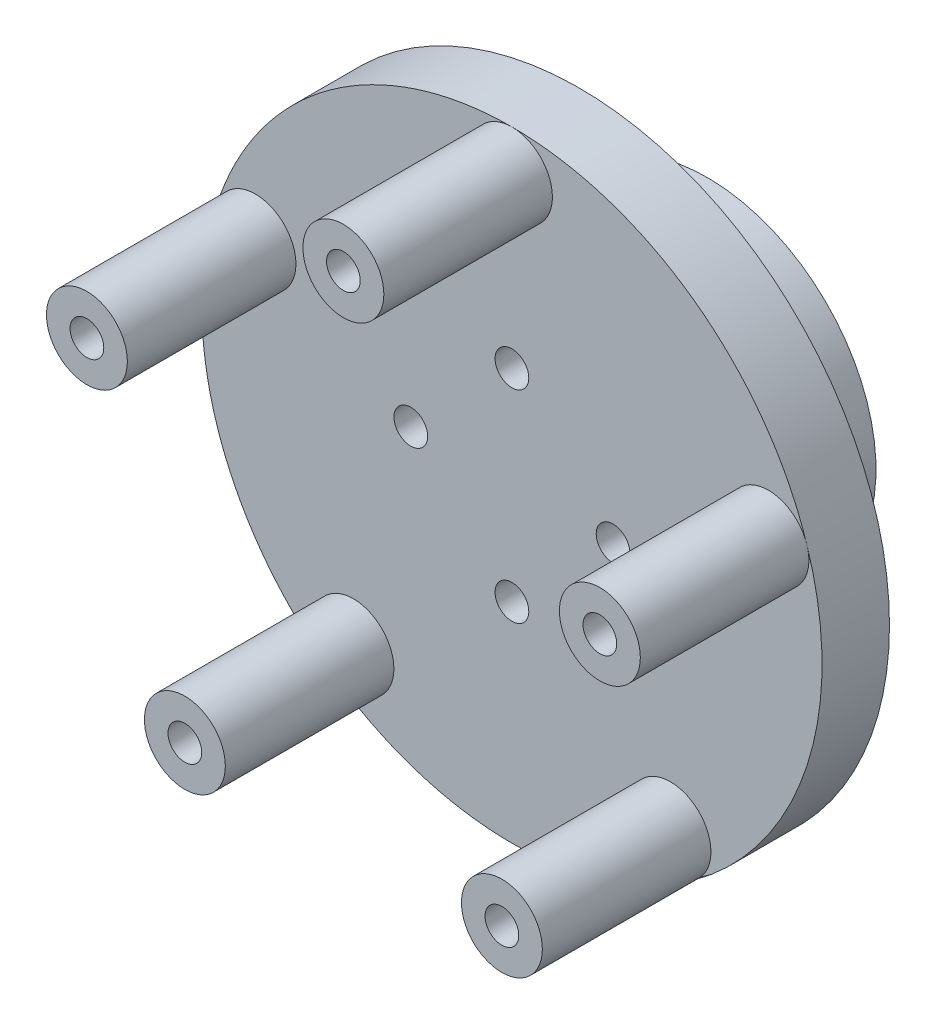
SolidWorks part; units mm, degrees
ref_plane "Front Plane" through (0, 0, 0) normal (0, 0, 1) x (1, 0, 0)
ref_plane "Top Plane" through (0, 0, 0) normal (0, 1, 0) x (1, 0, 0)
ref_plane "Right Plane" through (0, 0, 0) normal (1, 0, 0) x (0, 0, -1)
sketch "Sketch1" plane through (0, 0, 0) normal (0, 0, 1) x (1, 0, 0)
  circle A0 centre (0, 0) radius 20 construction
  circle A1 centre (0, 20) radius 3
  circle A2 centre (0, 0) radius 23
  dimension "D1" = 40
  dimension "D2" = 6
extrude "Boss-Extrude1" add sketch "Sketch1" along normal blind 5 contours A2
sketch "Sketch2" plane through (0, 0, 5) normal (0, 0, 1) x (1, 0, 0)
  circle A0 centre (0, 20) radius 3 construction
  circle A1 centre (0, 20) radius 3
  circle A2 centre (19.0211, 6.1803) radius 3
  circle A3 centre (11.7557, -16.1803) radius 3
  circle A4 centre (-11.7557, -16.1803) radius 3
  circle A5 centre (-19.0211, 6.1803) radius 3
  point P19 (0, 0)
  dimension "D1" = 5
extrude "Boss-Extrude2" add sketch "Sketch2" along normal blind 12.5 contours A5 | A4 | A3 | A2 | A1 region at (0, 20, 5) region at (19.0211, 6.1803, 5) region at (11.7557, -16.1803, 5) region at (-11.7557, -16.1803, 5) region at (-19.0211, 6.1803, 5)
sketch "Sketch3" plane through (0, 0, 0) normal (0, 0, -1) x (-1, 0, 0)
  circle A0 centre (0, 0) radius 12.5
  dimension "D1" = 25
extrude "Boss-Extrude3" add sketch "Sketch3" along normal blind 9.5
hole_wizard "M3 Tapped Hole1" positions "Sketch4" profile "Sketch5" tap size "M3" standard "ISO" end condition up to next
sketch "Sketch4" plane through (0, 0, 17.5) normal (0, 0, 1) x (1, 0, 0)
  point P0 (0, 20)
sketch "Sketch5" plane through (0, 20, 17.5) normal (1, 0, 0) x (0, -1, 0)
  line L0 (0, 0) -> (0, 17.5)
  line L1 (0, 17.5) -> (1.25, 17.5)
  line L2 (1.25, 17.5) -> (1.25, 0)
  line L5 (1.25, 0) -> (0, 0)
  line L11 (0, -6.35) -> (0, 107.95) construction
  dimension "Thru Tap Drill Dia." = 2.5
  dimension "Thru Tap Drill Depth" = 17.5
cosmetic thread "Hole Thread1" parameters "D2"=3
pattern_circular "CirPattern1" count 5 over 360 about axis through (0, 0, 5) along (0, 0, 1) of "M3 Tapped Hole1"
cosmetic thread "Hole Thread2" parameters "D2"=3
cosmetic thread "Hole Thread3" parameters "D2"=3
cosmetic thread "Hole Thread4" parameters "D2"=3
cosmetic thread "Hole Thread5" parameters "D2"=3
hole_wizard "M3 Tapped Hole2" positions "Sketch6" profile "Sketch8" tap size "M3" standard "ISO" end condition up to next
sketch "Sketch6" plane through (0, 0, -9.5) normal (0, 0, -1) x (-1, 0, 0)
  circle A0 centre (0, 0) radius 7.5
  point P5 (0, 7.5)
  point P7 (7.5, 0)
  point P9 (0, -7.5)
  point P11 (-7.5, 0)
  dimension "D1" = 15
sketch "Sketch8" plane through (7.5, 0, -9.5) normal (1, 0, 0) x (0, 1, 0)
  line L0 (0, 0) -> (0, 14.5)
  line L1 (0, 14.5) -> (1.25, 14.5)
  line L2 (1.25, 14.5) -> (1.25, 0)
  line L5 (1.25, 0) -> (0, 0)
  line L11 (0, -6.35) -> (0, 107.95) construction
  dimension "Thru Tap Drill Dia." = 2.5
  dimension "Thru Tap Drill Depth" = 14.5
cosmetic thread "Hole Thread6" parameters "D2"=3
cosmetic thread "Hole Thread7" parameters "D2"=3
cosmetic thread "Hole Thread8" parameters "D2"=3
cosmetic thread "Hole Thread9" parameters "D2"=3
equation "\"roller_radius\"= 6.5"
equation "\"eccentricity\"= \"roller_radius\" * 0.325"
equation "\"outer_radius\"= 40"
equation "\"eccentric_shaft_radius\"= 16"
equation "\"rotor_width\"= 10"
equation "\"housing_depth\"= 40"
equation "\"bottom_depth\"= 5"
equation "\"roller_bearing_OD\"= \"roller_radius\" * 2"
equation "\"roller_bearing_ID\"= 6"
equation "\"eccentric_bearing_ID\"= 6"
equation "\"eccentric_bearing_OD\"= 15"
equation "\"roller_bearing_height\"= 5"
equation "\"eccentric_bearing_height\"= 5"
equation "\"bottom_bearing_ID\"= 15"
equation "\"bottom_bearing_OD\"= 32"
equation "\"bottom_bearing_height\"= 9"
equation "\"distance_to_output_rotor_holes\"= 20"
equation "\"D1@Sketch1\"=\"distance_to_output_rotor_holes\"*2"
equation "\"D2@Sketch1\"=\"roller_bearing_ID\""
equation "\"D1@Boss-Extrude2\"=\"eccentric_bearing_height\"*2+2.5"
equation "\"D1@Sketch3\"=\"output_bearing_ID\""
equation "\"output_bearing_ID\" = 25"
equation "\"output_bearing_OD\" = 37"
equation "\"output_bearing_height\" = 7"
equation "\"D1@Boss-Extrude1\"=\"roller_bearing_height\""
equation "\"D1@Boss-Extrude3\"=\"output_bearing_height\"+\"spacer_3\"-\"roller_bearing_height\""
equation "\"number_of_rollers\" = 15"
equation "\"housing_height\" = 27"
equation "\"spacer_1\" = 7"
equation "\"spacer_2\" = 2.5"
equation "\"spacer_3\" = 7.5"
equation "\"roller_pin_depth\" = 5"
